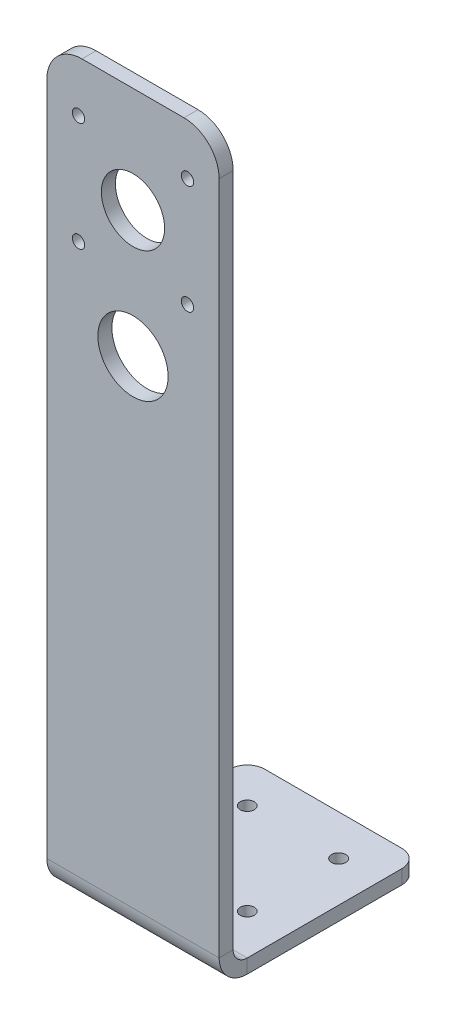
SolidWorks part; units mm, degrees
note: The reader was unsure of these and kept them because the rebuilt part matched: flange length of "Edge-Flange1".
ref_plane "Front Plane" through (0, 0, 0) normal (0, 0, 1) x (1, 0, 0)
ref_plane "Top Plane" through (0, 0, 0) normal (0, 1, 0) x (1, 0, 0)
ref_plane "Right Plane" through (0, 0, 0) normal (1, 0, 0) x (0, 0, -1)
sketch "Sketch1" plane through (0, 0, 0) normal (0, 1, 0) x (1, 0, 0)
  line L1 (-24.5, -24.5) -> (24.5, -24.5)
  line L2 (-24.5, -24.5) -> (-24.5, 24.5)
  line L3 (-24.5, 24.5) -> (24.5, 24.5)
  line L4 (24.5, -24.5) -> (24.5, 24.5)
  line L5 (-24.5, -24.5) -> (24.5, 24.5) construction
  line L6 (-24.5, 24.5) -> (24.5, -24.5) construction
  circle A0 centre (-13, -13) radius 2
  circle A1 centre (-13, 13) radius 2
  circle A2 centre (13, 13) radius 2
  circle A3 centre (13, -13) radius 2
  point P0 (0, 0)
  dimension "D2" = 4
  dimension "D3" = 26
  dimension "D1" = 49
base flange "Base-Flange1" sketch "Sketch1" thickness 4 reverse thickness direction no parameters "D1"=0.7366
edge flange "Edge-Flange1" sketch "Sketch8" flange angle 90 flange length 210 flange position bend outside bend radius 4 thickness 4 relief rectangular parameters "D6"=10
sketch "Sketch8" plane through (0, 0, 24.5) normal (0, 0, 1) x (1, 0, 0)
  line L0 (-24.5, 0) -> (24.5, 0) construction
  line L1 (-24.5, 0) -> (24.5, 0)
  line L2 (-24.5, 0) -> (-24.5, 206)
  line L3 (-24.5, 206) -> (24.5, 206)
  line L4 (24.5, 206) -> (24.5, 0)
bend "EdgeBend1" bend radius 4 bend angle 90 parameters "D5"=1
sketch "Sketch9" plane through (0, 0, 28.5) normal (0, 0, -1) x (-1, 0, 0)
  line L0 (24.5, 0) -> (-24.5, 0) construction
  circle A0 centre (0, 140) radius 10
  point P4 (0, 0)
  dimension "D1" = 20
  dimension "D2" = 140
extrude "Cut-Extrude1" cut sketch "Sketch9" against normal blind 10 normal cut yes
sketch "Sketch10" plane through (0, 0, 28.5) normal (0, 0, -1) x (-1, 0, 0)
  circle A0 centre (0, 176) radius 9
  circle A1 centre (0, 140) radius 10 construction
  circle A2 centre (0, 140) radius 10
  circle A3 centre (-15.5, 160.5) radius 1.75
  circle A4 centre (-15.5, 191.5) radius 1.75
  circle A5 centre (15.5, 191.5) radius 1.75
  circle A6 centre (15.5, 160.5) radius 1.75
  dimension "D1" = 18
  dimension "D3" = 3.5
  dimension "D4" = 31
  dimension "D2" = 36
  dimension "D5" = 15.5
  dimension "D6" = 31
  dimension "D7" = 15.5
extrude "Cut-Extrude2" cut sketch "Sketch10" against normal through all normal cut yes
fillet "Fillet1" radius 10 2 edges at (24.5, 206, 30.5) (-24.5, 206, 30.5)
fillet "Fillet2" radius 5 2 edges at (-24.5, -2, -24.5) (24.5, -2, -24.5)
sketch "Bend-Lines1" [suppressed] plane through (0, 0, 0) normal (0, 1, 0) x (1, 0, 0)
sketch "Bounding-Box1" [suppressed] plane through (0, 0, 0) normal (0, 1, 0) x (1, 0, 0)
sheet metal parameters "Sheet-Metal1" thickness 4 parameters "D1"=0.7366
flat pattern "Flat-Pattern1" [suppressed]
sketch "Bend-Lines2" plane through (0, 0, 0) normal (0, 1, 0) x (1, 0, 0)
sketch3d "Bounding-Box2" [suppressed]
  line L0 (-17.5, -17.5, 0) -> (-17.5, 17.5, 0) construction
  line L1 (17.5, -17.5, 0) -> (17.5, 17.5, 0) construction
  line L2 (-17.5, -17.5, 0) -> (17.5, -17.5, 0) construction
  line L3 (-17.5, 17.5, 0) -> (17.5, 17.5, 0) construction
sheet metal parameters "Sheet-Metal2" thickness 4 parameters "D1"=0.7366
flat pattern "Flat-Pattern1"
sketch "Bend-Lines2" plane through (0, 0, 0) normal (0, 1, 0) x (1, 0, 0)
  line L0 (-17.5, -19.6493) -> (17.5, -19.6493) construction
  line L1 (-17.5, -19.6493) -> (17.5, -19.6493) construction
sketch3d "Bounding-Box2" [suppressed]
  line L0 (-17.5, -217.062, 0) -> (-17.5, 17.5, 0) construction
  line L1 (17.5, -217.062, 0) -> (17.5, 17.5, 0) construction
  line L2 (-17.5, -217.062, 0) -> (17.5, -217.062, 0) construction
  line L3 (-17.5, 17.5, 0) -> (17.5, 17.5, 0) construction
bend of the flat pattern "Flatten-<EdgeBend1>1"
sheet metal parameters "Sheet-Metal3" thickness 4 parameters "D1"=0.7366
flat pattern "Flat-Pattern1"
sketch "Bend-Lines2" plane through (0, 0, 0) normal (0, 1, 0) x (1, 0, 0)
  line L0 (-17.5, -19.6493) -> (17.5, -19.6493) construction
  line L1 (-17.5, -19.6493) -> (17.5, -19.6493) construction
sketch3d "Bounding-Box2" [suppressed]
  line L0 (-17.5, -217.062, 0) -> (-17.5, 17.5, 0) construction
  line L1 (17.5, -217.062, 0) -> (17.5, 17.5, 0) construction
  line L2 (-17.5, -217.062, 0) -> (17.5, -217.062, 0) construction
  line L3 (-17.5, 17.5, 0) -> (17.5, 17.5, 0) construction
bend of the flat pattern "Flatten-<EdgeBend1>1"
sheet metal parameters "Sheet-Metal4" thickness 4 parameters "D1"=0.7366
flat pattern "Flat-Pattern1"
sketch "Bend-Lines2" plane through (0, 0, 0) normal (0, 1, 0) x (1, 0, 0)
  line L0 (-24.5, -29.2124) -> (24.5, -29.2124) construction
  line L1 (-24.5, -29.2124) -> (24.5, -29.2124) construction
sketch3d "Bounding-Box2" [suppressed]
  line L0 (24.5, -235.9248, 0) -> (24.5, 24.5, 0) construction
  line L1 (-24.5, -235.9248, 0) -> (-24.5, 24.5, 0) construction
  line L2 (24.5, -235.9248, 0) -> (-24.5, -235.9248, 0) construction
  line L3 (24.5, 24.5, 0) -> (-24.5, 24.5, 0) construction
bend of the flat pattern "Flatten-<EdgeBend1>1"
